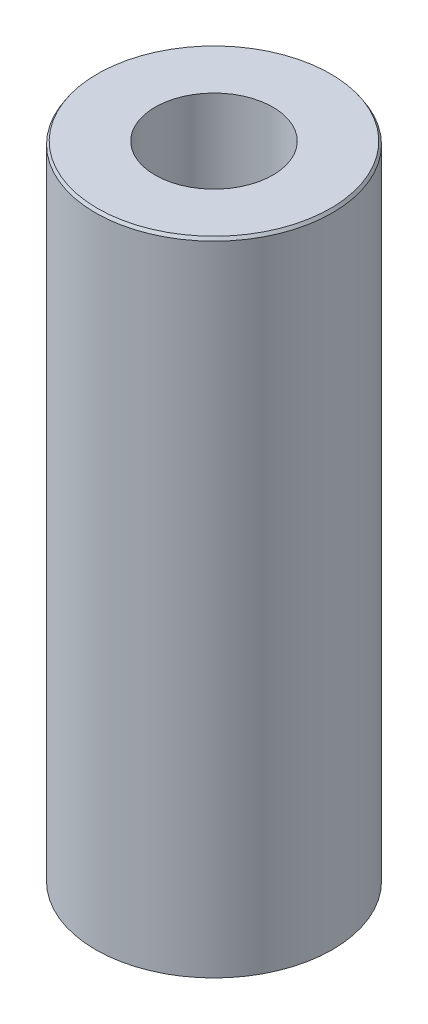
SolidWorks part; units mm, degrees
ref_plane "Front Plane" through (0, 0, 0) normal (0, 0, 1) x (1, 0, 0)
ref_plane "Top Plane" through (0, 0, 0) normal (0, 1, 0) x (1, 0, 0)
ref_plane "Right Plane" through (0, 0, 0) normal (1, 0, 0) x (0, 0, -1)
sketch "Sketch1" plane through (0, 0, 0) normal (0, 1, 0) x (1, 0, 0)
  circle A0 centre (0, 0) radius 50
  dimension "SHAFT_OD" = 100
extrude "Boss-Extrude1" add sketch "Sketch1" along normal blind 271.3834
sketch "Sketch2" plane through (0, 0, 0) normal (0, 1, 0) x (1, 0, 0)
  circle A0 centre (0, 0) radius 24.8639
  dimension "BORE_D" = 49.7277
extrude "Cut-Extrude1" cut sketch "Sketch2" along normal through all
chamfer "Chamfer1" distance 1.2393 angle 32.897 2 edges at (0, 271.3834, 50) (0, 0, 50) first distance on face at (0, 271.3834, 50) first distance on face at (0, 0, 24.8639)
